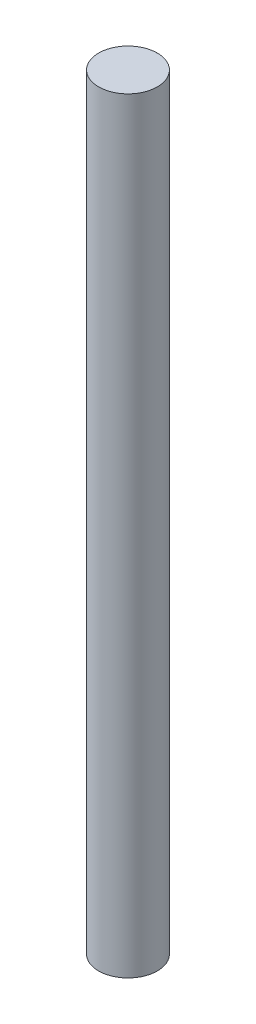
SolidWorks part; units mm, degrees
ref_plane "Front Plane" through (0, 0, 0) normal (0, 0, 1) x (1, 0, 0)
ref_plane "Top Plane" through (0, 0, 0) normal (0, 1, 0) x (1, 0, 0)
ref_plane "Right Plane" through (0, 0, 0) normal (1, 0, 0) x (0, 0, -1)
sketch "Sketch1" plane through (0, 0, 0) normal (0, 1, 0) x (1, 0, 0)
  circle A0 centre (0, 0) radius 2
  dimension "D1" = 4
extrude "Boss-Extrude1" add sketch "Sketch1" along normal blind 52.2
